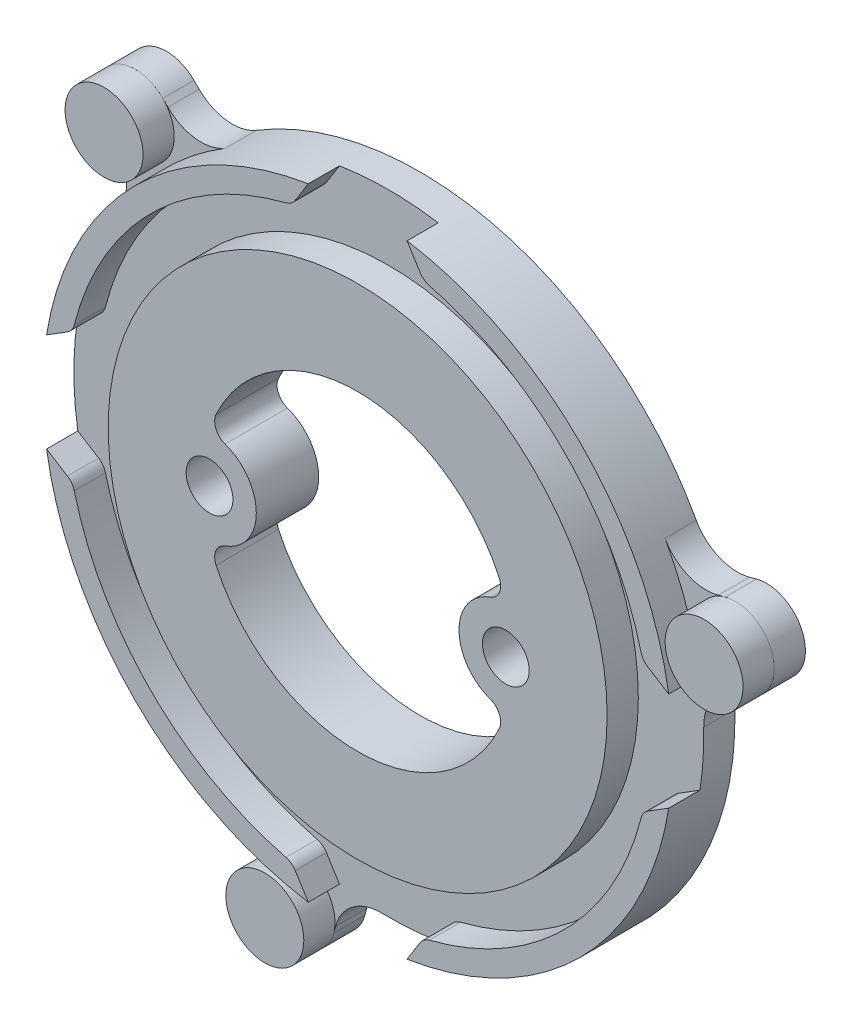
SolidWorks part; units mm, degrees
material "ABS"
ref_plane "Front Plane" through (0, 0, 0) normal (0, 0, 1) x (1, 0, 0)
ref_plane "Top Plane" through (0, 0, 0) normal (0, 1, 0) x (1, 0, 0)
ref_plane "Right Plane" through (0, 0, 0) normal (1, 0, 0) x (0, 0, -1)
sketch "Sketch2" plane through (0, 0, 0) normal (0, 0, 1) x (1, 0, 0)
  circle A0 centre (0, 0) radius 20.2
  dimension "D1" = 40.4
extrude "Boss-Extrude3" add sketch "Sketch2" along normal blind 2 and the other way blind 2
sketch "Sketch3" plane through (0, 0, 0) normal (0, 0, 1) x (1, 0, 0)
  circle A0 centre (0, 0) radius 18.75
  circle A1 centre (0, 0) radius 16
  dimension "D1" = 37.5
  dimension "D2" = 32
extrude "Cut-Extrude1" cut sketch "Sketch3" along normal through all
sketch "Sketch4" plane through (0, 0, 0) normal (0, 0, 1) x (1, 0, 0)
  line L0 (-4.2178, 18.2694) -> (-4.544, 19.6823) construction
  line L1 (4.2178, 18.2694) -> (4.544, 19.6823) construction
  line L2 (0, 0) -> (-4.2178, 18.2694) construction
  line L3 (0, 0) -> (4.2178, 18.2694) construction
  line L4 (-4.2178, 18.2694) -> (-3.1676, 19.9501)
  line L5 (4.2178, 18.2694) -> (3.1676, 19.9501)
  circle A0 centre (0, 0) radius 20.2 construction
  circle A1 centre (0, 0) radius 18.75 construction
  arc A2 (3.1676, 19.9501) -> (-3.1676, 19.9501) centre (0, 0) ccw
  arc A3 (4.2178, 18.2694) -> (-4.2178, 18.2694) centre (0, 0) ccw
  arc A4 (-3.1676, 19.9501) -> (-4.544, 19.6823) centre (0, 0) ccw construction
  arc A5 (4.544, 19.6823) -> (3.1676, 19.9501) centre (0, 0) ccw construction
  point P4 (0, 20.2)
  dimension "D1" = 26
  dimension "D2" = 45
  dimension "D3" = 45
extrude "Cut-Extrude2" cut sketch "Sketch4" along normal through all
fillet "Fillet1" radius 1 2 edges at (4.2178, 18.2694, 1) (-4.2178, 18.2694, 1)
pattern_circular "CirPattern1" count 4 over 360 about axis through (0, 0, -2) along (0, 0, 1) of "Fillet1", "Cut-Extrude2"
sketch "Sketch6" plane through (0, 0, 0) normal (0, 0, 1) x (1, 0, 0)
  line L0 (-9.5, 0) -> (9.5, 0) construction
  arc A0 (-9.5395, -2.9997) -> (9.5395, -2.9997) centre (0, 0) ccw
  arc A1 (-9.5395, -2.9997) -> (-9.5395, 2.9997) centre (-9.5, 0) ccw
  arc A2 (9.5395, 2.9997) -> (9.5395, -2.9997) centre (9.5, 0) ccw
  arc A3 (-9.5395, 2.9997) -> (-9.5395, -2.9997) centre (0, 0) ccw construction
  arc A4 (-9.5395, 2.9997) -> (-9.5395, -2.9997) centre (-9.5, 0) ccw construction
  arc A5 (9.5395, -2.9997) -> (9.5395, 2.9997) centre (9.5, 0) ccw construction
  arc A6 (9.5395, 2.9997) -> (-9.5395, 2.9997) centre (0, 0) ccw
  arc A7 (9.5395, -2.9997) -> (9.5395, 2.9997) centre (0, 0) ccw construction
  point P5 (0, 0)
  dimension "D2" = 6
  dimension "D3" = 20
  dimension "D1" = 19
extrude "Cut-Extrude3" cut sketch "Sketch6" against normal through all both and the other way through all
fillet "Fillet2" radius 1 4 edges at (9.5395, 2.9997, 0) (9.5395, -2.9997, 0) (-9.5395, -2.9997, 0) (-9.5395, 2.9997, 0)
sketch "Sketch8" plane through (0, 0, 0) normal (0, 0, 1) x (1, 0, 0)
  line L0 (-9.5, 0) -> (9.5, 0) construction
  circle A0 centre (9.5, 0) radius 1.5
  circle A1 centre (-9.5, 0) radius 1.5
  point P5 (0, 0)
  dimension "D1" = 3
  dimension "D2" = 19
extrude "Cut-Extrude4" cut sketch "Sketch8" against normal through all both and the other way through all
sketch "Sketch9" plane through (0, 0, 0) normal (0, 0, 1) x (1, 0, 0)
  line L0 (-16.2635, 16.2635) -> (0, 0) construction
  line L1 (0, 33.0392) -> (0, -32.7246) construction
  line L2 (-14.4957, 18.0312) -> (-12.406, 15.9415)
  line L3 (-18.0312, 14.4957) -> (-15.9415, 12.406)
  circle A0 centre (0, 0) radius 23 construction
  arc A1 (-14.4022, 17.9325) -> (-17.9325, 14.4022) centre (-16.2635, 16.2635) ccw
  arc A2 (-3.1676, 19.9501) -> (-19.9501, 3.1676) centre (0, 0) ccw construction
  arc A3 (-12.406, 15.9415) -> (-15.9415, 12.406) centre (0, 0) ccw
  arc A4 (-14.4957, 14.4957) -> (-14.4022, 17.9325) centre (-16.2635, 16.2635) ccw construction
  arc A5 (-17.9325, 14.4022) -> (-14.4957, 14.4957) centre (-16.2635, 16.2635) ccw construction
  arc A6 (-15.9415, 12.406) -> (-19.9501, 3.1676) centre (0, 0) ccw construction
  arc A7 (-3.1676, 19.9501) -> (-12.406, 15.9415) centre (0, 0) ccw construction
  dimension "D1" = 46
  dimension "D3" = 5
  dimension "D2" = 45
extrude "Boss-Extrude4" add sketch "Sketch9" against normal up to surface (2 mm away) contours A3 L2 A1 L3 region at (-15.9721, 15.9721, 0) up to face at (11, 0, -2)
sketch "Sketch10" plane through (0, 0, 0) normal (0, 0, 1) x (1, 0, 0)
  circle A0 centre (-16.2635, 16.2635) radius 1.6375
  dimension "D1" = 3.275
extrude "Cut-Extrude5" cut sketch "Sketch10" against normal blind 1.7
fillet "Fillet3" radius 3 2 edges at (-15.9415, 12.406, -1) (-12.406, 15.9415, -1)
pattern_circular "CirPattern2" count 3 over 360 about axis through (0, 0, 2) along (0, 0, 1) of "Boss-Extrude4", "Cut-Extrude5", "Fillet3"
sketch "Sketch13" plane through (0, 0, 0) normal (0, 0, 1) x (1, 0, 0)
  arc A0 (-14.4957, 18.0312) -> (-18.0312, 14.4957) centre (-16.2635, 16.2635) ccw construction
  circle A1 centre (-16.2635, 16.2635) radius 1.6375 construction
  arc A2 (-14.4957, 18.0312) -> (-18.0312, 14.4957) centre (-16.2635, 16.2635) ccw
  circle A3 centre (-16.2635, 16.2635) radius 1.6375
  circle A4 centre (-16.2635, 16.2635) radius 2.5
extrude "Boss-Extrude5" add sketch "Sketch13" along normal blind 2 separate body contours A2 A4 A3 region at (-14.0191, 17.1931, 0)
sketch "Sketch14" plane through (0, 0, 2) normal (0, 0, 1) x (1, 0, 0)
  circle A0 centre (-16.2635, 16.2635) radius 2.5 construction
  circle A1 centre (-16.2635, 16.2635) radius 2.5
extrude "Boss-Extrude6" add sketch "Sketch14" against normal offset from surface (0.4 mm away) 1.6 up to face at (-14.626, 16.2635, 0)
pattern_circular "CirPattern3" count 3 over 360 about axis through (0, 0, 2) along (0, 0, 1) of bodies 114
equation "\"magnet_circle_diameter\"= 46mm"
equation "\"holoprojector_ID\"= 32mm"
equation "\"D1@Sketch2\"=40.4mm"
equation "\"mount_thickness\"= 2mm"
equation "\"D2@Boss-Extrude3\"=\"mount_thickness\""
equation "\"holoprojector_tab_height\"= 2mm"
equation "\"D1@Boss-Extrude3\"=\"holoprojector_tab_height\""
equation "\"D1@Sketch9\"=\"magnet_circle_diameter\""
equation "\"D1@Boss-Extrude5\"=\"holoprojector_tab_height\""
